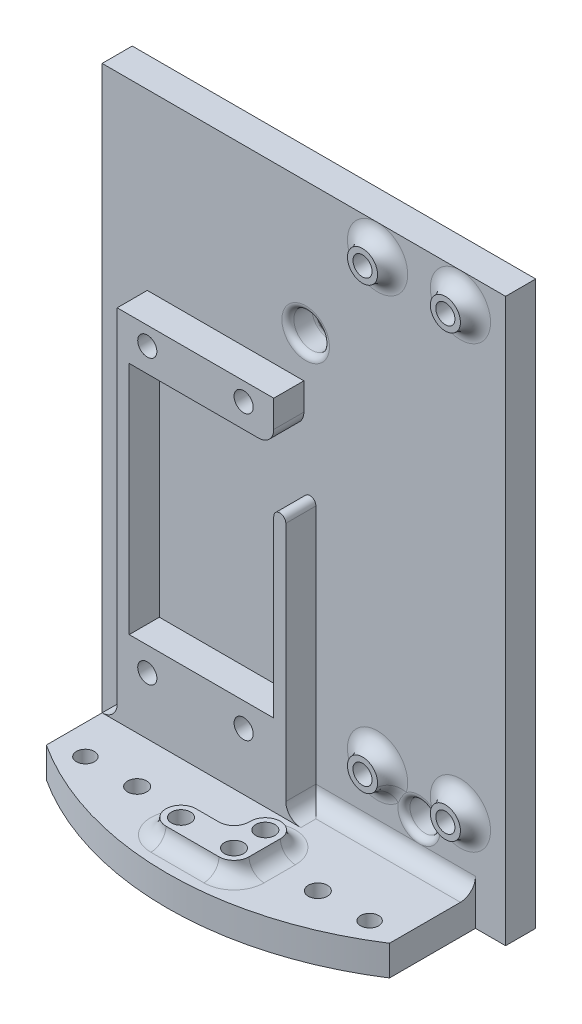
SolidWorks part; units mm, degrees
ref_plane "Front Plane" through (0, 0, 0) normal (0, 0, 1) x (1, 0, 0)
ref_plane "Top Plane" through (0, 0, 0) normal (0, 1, 0) x (1, 0, 0)
ref_plane "Right Plane" through (0, 0, 0) normal (1, 0, 0) x (0, 0, -1)
sketch "Sketch1" plane through (0, 0, 0) normal (0, 0, 1) x (1, 0, 0)
  line L1 (0, 0) -> (85.09, 0)
  line L2 (0, 0) -> (0, 118.618)
  line L3 (0, 118.618) -> (85.09, 118.618)
  line L4 (85.09, 0) -> (85.09, 118.618)
  dimension "D1" = 118.618
  dimension "D2" = 85.09
extrude "Boss1 - Main Plate" add sketch "Sketch1" along normal blind 6.35 contours L2 L1 L4 L3
sketch "Sketch2" plane through (0, 0, 0) normal (0, -1, 0) x (1, 0, 0)
  line L0 (6.35, 24.4739) -> (6.35, 0)
  line L1 (78.74, 24.4739) -> (78.74, 0)
  line L2 (6.35, 0) -> (78.74, 0)
  line L3 (0, 0) -> (85.09, 0) construction
  line L4 (85.09, 6.35) -> (85.09, 0) construction
  arc A0 (78.74, 24.4739) -> (6.35, 24.4739) centre (42.545, -31.5214) ccw
  dimension "D1" = 133.35
  dimension "D2" = 6.35
  dimension "D3" = 6.35
  dimension "D4" = 31.5214
  dimension "D5" = 42.545
  dimension "D6" = 0
extrude "Boss2 - Bottom Plate" add sketch "Sketch2" along direction (0, 1, 0) on the side against the normal offset from surface (6.35 mm away) 6.35 up to plane "Top Plane"
sketch "Sketch3" plane through (0, 0, 6.35) normal (0, 0, 1) x (1, 0, 0)
  line L0 (78.74, 6.35) -> (6.35, 6.35) construction
  line L1 (9.525, 6.35) -> (45.085, 6.35)
  line L2 (9.525, 6.35) -> (9.525, 23.495)
  line L3 (12.065, 23.495) -> (42.545, 23.495)
  line L4 (45.085, 6.35) -> (45.085, 23.495)
  line L7 (9.525, 23.495) -> (9.525, 73.025)
  line L9 (12.065, 23.495) -> (12.065, 73.025)
  line L11 (45.085, 23.495) -> (45.085, 60.325)
  line L13 (42.545, 23.495) -> (42.545, 60.325)
  line L14 (12.065, 73.025) -> (39.37, 73.025)
  line L15 (9.525, 73.025) -> (9.525, 81.915)
  line L16 (9.525, 81.915) -> (42.545, 81.915)
  line L17 (42.545, 76.2) -> (42.545, 81.915)
  line L19 (85.09, 0) -> (85.09, 118.618) construction
  line L20 (78.74, 0) -> (85.09, 0) construction
  arc A1 (45.085, 60.325) -> (42.545, 60.325) centre (43.815, 60.325) ccw
  arc A2 (39.37, 73.025) -> (42.545, 76.2) centre (39.37, 76.2) ccw
  point P26 (42.545, 73.025)
  dimension "D9" = 60.325
  dimension "D14" = 3.175
  dimension "D1" = 3.175
  dimension "D2" = 0
  dimension "D3" = 17.145
  dimension "D4" = 35.56
  dimension "D5" = 49.53
  dimension "D6" = 33.02
  dimension "D7" = 2.54
  dimension "D8" = 2.54
  dimension "D10" = 8.89
  dimension "D11" = 36.83
  dimension "D12" = 118.618
  dimension "D13" = 118.618
extrude "Boss3 - Battery Plate" add sketch "Sketch3" along normal blind 6.35
fillet "Fillet1 - Plate Convergence" radius 3.175 4 edges at (7.9375, 6.35, 6.35) (9.525, 6.35, 9.525) (45.085, 6.35, 9.525) (61.9125, 6.35, 6.35)
hole_wizard "Holes1 - Main Plate" positions "Sketch4" profile "Sketch5" hole size "1/4" standard "ANSI Inch" end condition through all
sketch "Sketch4" plane through (0, 0, 0) normal (0, 0, -1) x (-1, 0, 0)
  line L2 (0, 0) -> (-85.09, 0) construction
  line L3 (0, 0) -> (0, 118.618) construction
  point P8 (-36.195, 18.415)
  point P10 (-15.875, 18.415)
  point P12 (-15.875, 78.105)
  point P14 (-36.195, 78.105)
  dimension "D9" = 15.875
  dimension "D10" = 15.875
  dimension "D11" = 20.32
  dimension "D12" = 20.32
  dimension "D13" = 18.415
  dimension "D14" = 18.415
  dimension "D15" = 59.69
  dimension "D16" = 59.69
sketch "Sketch5" plane through (36.195, 18.415, 0) normal (1, 0, 0) x (0, 1, 0)
  line L0 (0, 0) -> (0, 35.1536)
  line L1 (0, 35.1536) -> (2.0193, 35.1536)
  line L2 (2.0193, 35.1536) -> (2.0193, 0)
  line L5 (2.0193, 0) -> (0, 0)
  line L11 (0, -6.35) -> (0, 107.95) construction
  dimension "Thru Hole Dia." = 4.0386
  dimension "Thru Hole Depth" = 35.1536
hole_wizard "Holes2 - Top Main Plate" positions "Sketch6" profile "Sketch7" hole size "1/4" standard "ANSI Inch" end condition through all
sketch "Sketch6" plane through (0, 0, 0) normal (0, 0, -1) x (-1, 0, 0)
  line L0 (0, 118.618) -> (-85.09, 118.618) construction
  line L1 (0, 0) -> (0, 118.618) construction
  point P0 (-42.926, 90.805)
  dimension "D1" = 27.813
  dimension "D2" = 42.926
sketch "Sketch7" plane through (42.926, 90.805, 0) normal (1, 0, 0) x (0, 1, 0)
  line L0 (0, 0) -> (0, 35.1536)
  line L1 (0, 35.1536) -> (3.7465, 35.1536)
  line L2 (3.7465, 35.1536) -> (3.7465, 0)
  line L5 (3.7465, 0) -> (0, 0)
  line L11 (0, -6.35) -> (0, 107.95) construction
  dimension "Thru Hole Dia." = 7.493
  dimension "Thru Hole Depth" = 35.1536
hole_wizard "Holes3 - Bot Main Plate" positions "Sketch8" profile "Sketch9" hole size "1/4" standard "ANSI Inch" end condition through all
sketch "Sketch8" plane through (0, 0, 0) normal (0, 0, -1) x (-1, 0, 0)
  line L0 (-85.09, 0) -> (-85.09, 118.618) construction
  line L1 (0, 0) -> (-85.09, 0) construction
  point P0 (-66.8274, 13.97)
  dimension "D1" = 18.2626
  dimension "D2" = 13.97
sketch "Sketch9" plane through (66.8274, 13.97, 0) normal (1, 0, 0) x (0, 1, 0)
  line L0 (0, 0) -> (0, 35.1536)
  line L1 (0, 35.1536) -> (3.175, 35.1536)
  line L2 (3.175, 35.1536) -> (3.175, 0)
  line L5 (3.175, 0) -> (0, 0)
  line L11 (0, -6.35) -> (0, 107.95) construction
  dimension "Thru Hole Dia." = 6.35
  dimension "Thru Hole Depth" = 35.1536
fillet "Fillet1 - Holes Main Plate" radius 1.27 4 edges at (63.6524, 13.97, 0) (70.0024, 13.97, 6.35) (46.6725, 90.805, 6.35) (39.1795, 90.805, 0)
hole_wizard "Holes4 - Bottom Plate" positions "Sketch10" profile "Sketch11" hole size "1/4" standard "ANSI Inch" end condition through all
sketch "Sketch10" plane through (0, 0, 0) normal (0, -1, 0) x (-1, 0, 0)
  line L0 (-6.35, -24.4739) -> (-6.35, -6.35) construction
  line L1 (-78.74, -6.35) -> (-78.74, -24.4739) construction
  line L2 (0, 0) -> (-85.09, 0) construction
  point P0 (-23.495, -22.4536)
  point P2 (-61.595, -22.4536)
  dimension "D1" = 17.145
  dimension "D2" = 17.145
  dimension "D3" = 22.4536
  dimension "D4" = 22.4536
sketch "Sketch11" plane through (23.495, 0, 22.4536) normal (1, 0, 0) x (0, 0, -1)
  line L0 (0, 0) -> (0, 118.618)
  line L1 (0, 118.618) -> (2.0193, 118.618)
  line L2 (2.0193, 118.618) -> (2.0193, 0)
  line L5 (2.0193, 0) -> (0, 0)
  line L11 (0, -6.35) -> (0, 107.95) construction
  dimension "Thru Hole Dia." = 4.0386
  dimension "Thru Hole Depth" = 118.618
hole_wizard "Holes6" positions "Sketch14" profile "Sketch15" hole size "#6" standard "ANSI Inch" end condition through all
sketch "Sketch14" plane through (0, 6.35, 0) normal (0, 1, 0) x (1, 0, 0)
  circle A0 centre (23.495, -22.4536) radius 2.0193 construction
  circle A1 centre (61.595, -22.4536) radius 2.0193 construction
  point P0 (72.517, -22.4536)
  point P2 (12.573, -22.4536)
  dimension "D1" = 10.922
  dimension "D2" = 10.922
  dimension "D3" = 0
  dimension "D4" = 0
sketch "Sketch15" plane through (72.517, 6.35, 22.4536) normal (1, 0, 0) x (0, 0, 1)
  line L0 (0, 0) -> (0, 6.35)
  line L1 (0, 6.35) -> (1.8986, 6.35)
  line L2 (1.8986, 6.35) -> (1.8986, 0)
  line L5 (1.8986, 0) -> (0, 0)
  line L11 (0, -6.35) -> (0, 107.95) construction
  dimension "Thru Hole Dia." = 3.7973
  dimension "Thru Hole Depth" = 6.35
sketch "Sketch17" plane through (0, 6.35, 0) normal (0, 1, 0) x (1, 0, 0)
  line L0 (6.35, -24.4739) -> (6.35, -12.7) construction
  line L1 (78.74, -9.525) -> (78.74, -24.4739) construction
  line L2 (0, 0) -> (85.09, 0) construction
  line L3 (36.957, -23.495) -> (41.783, -23.495)
  line L4 (36.957, -29.845) -> (48.133, -29.845)
  line L5 (44.958, -20.066) -> (44.958, -20.32)
  line L6 (51.308, -20.066) -> (51.308, -26.67)
  arc A0 (51.308, -20.066) -> (44.958, -20.066) centre (48.133, -20.066) ccw
  arc A1 (36.957, -23.495) -> (36.957, -29.845) centre (36.957, -26.67) ccw
  arc A2 (48.133, -29.845) -> (51.308, -26.67) centre (48.133, -26.67) ccw
  arc A3 (44.958, -20.32) -> (41.783, -23.495) centre (41.783, -20.32) cw
  point P0 (36.957, -26.67)
  point P1 (48.133, -26.67)
  point P2 (48.133, -20.066)
  dimension "D17" = 3.175
  dimension "D1" = 30.607
  dimension "D2" = 30.607
  dimension "D3" = 30.607
  dimension "D4" = 26.67
  dimension "D5" = 20.066
  dimension "D6" = 6.604
  dimension "D7" = 0
  dimension "D8" = 0
  dimension "D9" = 3.175
  dimension "D10" = 3.175
  dimension "D11" = 3.175
  dimension "D12" = 3.175
  dimension "D13" = 0
  dimension "D14" = 0
  dimension "D15" = 0
  dimension "D16" = 0
extrude "Boss4 - Bottom Plate Standoff" add sketch "Sketch17" along normal blind 3.175
hole_wizard "Holes7 - Bottom Plate" positions "Sketch18" profile "Sketch19" hole size "1/4" standard "ANSI Inch" end condition through all
sketch "Sketch18" plane through (0, 9.525, 0) normal (0, 1, 0) x (1, 0, 0)
  arc A0 (36.957, -23.495) -> (36.957, -29.845) centre (36.957, -26.67) ccw construction
  arc A1 (48.133, -29.845) -> (51.308, -26.67) centre (48.133, -26.67) ccw construction
  arc A2 (51.308, -20.066) -> (44.958, -20.066) centre (48.133, -20.066) ccw construction
  point P0 (36.957, -26.67)
  point P2 (48.133, -26.67)
  point P4 (48.133, -20.066)
  dimension "D1" = 0
  dimension "D2" = 0
  dimension "D3" = 0
sketch "Sketch19" plane through (36.957, 9.525, 26.67) normal (1, 0, 0) x (0, 0, 1)
  line L0 (0, 0) -> (0, 9.525)
  line L1 (0, 9.525) -> (2.0193, 9.525)
  line L2 (2.0193, 9.525) -> (2.0193, 0)
  line L5 (2.0193, 0) -> (0, 0)
  line L11 (0, -6.35) -> (0, 107.95) construction
  dimension "Thru Hole Dia." = 4.0386
  dimension "Thru Hole Depth" = 9.525
fillet "Fillet2 - Bottom Plate" radius 3.175 8 edges at (39.37, 6.35, 23.495) (44.0281, 6.35, 22.5651) (44.958, 6.35, 20.193) (48.133, 6.35, 16.891) (51.308, 6.35, 23.368) (50.3781, 6.35, 28.9151) (33.782, 6.35, 26.67) (42.545, 6.35, 29.845)
sketch "Sketch21" plane through (0, 0, 6.35) normal (0, 0, 1) x (1, 0, 0)
  line L0 (85.09, 0) -> (85.09, 118.618) construction
  line L1 (0, 118.618) -> (85.09, 118.618) construction
  line L2 (78.74, 0) -> (85.09, 0) construction
  circle A0 centre (58.0898, 112.268) radius 3.175
  circle A1 centre (75.565, 112.268) radius 3.175
  circle A2 centre (58.0898, 19.4056) radius 3.175
  circle A3 centre (75.565, 19.4056) radius 3.175
  point P0 (58.0898, 112.268)
  point P1 (75.565, 112.268)
  point P2 (75.565, 19.4056)
  point P3 (58.0898, 19.4056)
  dimension "D9" = 6.35
  dimension "D10" = 6.35
  dimension "D11" = 6.35
  dimension "D12" = 6.35
  dimension "D1" = 9.525
  dimension "D2" = 9.525
  dimension "D3" = 6.35
  dimension "D4" = 6.35
  dimension "D5" = 17.4752
  dimension "D6" = 19.4056
  dimension "D7" = 17.4752
  dimension "D8" = 19.4056
  dimension "D13" = 92.8624
extrude "Boss5 - Main Plate Standoffs" add sketch "Sketch21" along normal blind 3.175
fillet "Fillet3 - Main Plate Standoffs" radius 3.175 4 edges at (61.2648, 19.4056, 6.35) (78.74, 19.4056, 6.35) (61.2648, 112.268, 6.35) (78.74, 112.268, 6.35)
hole_wizard "Holes8 - Main Plate" positions "Sketch22" profile "Sketch23" hole size "1/4" standard "ANSI Inch" end condition through all
sketch "Sketch22" plane through (0, 0, 9.525) normal (0, 0, 1) x (1, 0, 0)
  arc A0 (61.1217, 18.4633) -> (60.2751, 17.1023) centre (58.0898, 19.4056) ccw construction
  arc A1 (73.3797, 17.1023) -> (72.5331, 18.4633) centre (75.565, 19.4056) ccw construction
  circle A3 centre (58.0898, 112.268) radius 3.175 construction
  circle A4 centre (75.565, 112.268) radius 3.175 construction
  point P0 (58.0898, 112.268)
  point P2 (75.565, 112.268)
  point P4 (75.565, 19.4056)
  point P5 (58.0898, 19.4056)
  dimension "D1" = 0
  dimension "D2" = 0
  dimension "D3" = 0
  dimension "D4" = 0
sketch "Sketch23" plane through (58.0898, 112.268, 9.525) normal (1, 0, 0) x (0, -1, 0)
  line L0 (0, 0) -> (0, 9.525)
  line L1 (0, 9.525) -> (2.0193, 9.525)
  line L2 (2.0193, 9.525) -> (2.0193, 0)
  line L5 (2.0193, 0) -> (0, 0)
  line L11 (0, -6.35) -> (0, 107.95) construction
  dimension "Thru Hole Dia." = 4.0386
  dimension "Thru Hole Depth" = 9.525
equation "\"D10@Sketch4\"=\"D9@Sketch4\""
equation "\"D12@Sketch4\"=\"D11@Sketch4\""
equation "\"D14@Sketch4\"=\"D13@Sketch4\""
equation "\"D16@Sketch4\"=\"D15@Sketch4\""
equation "\"D2@Sketch10\"=\"D1@Sketch10\""
equation "\"D4@Sketch10\"=\"D3@Sketch10\""
equation "\"D10@Sketch21\"=\"D9@Sketch21\""
equation "\"D11@Sketch21\"=\"D9@Sketch21\""
equation "\"D12@Sketch21\"=\"D10@Sketch21\""
